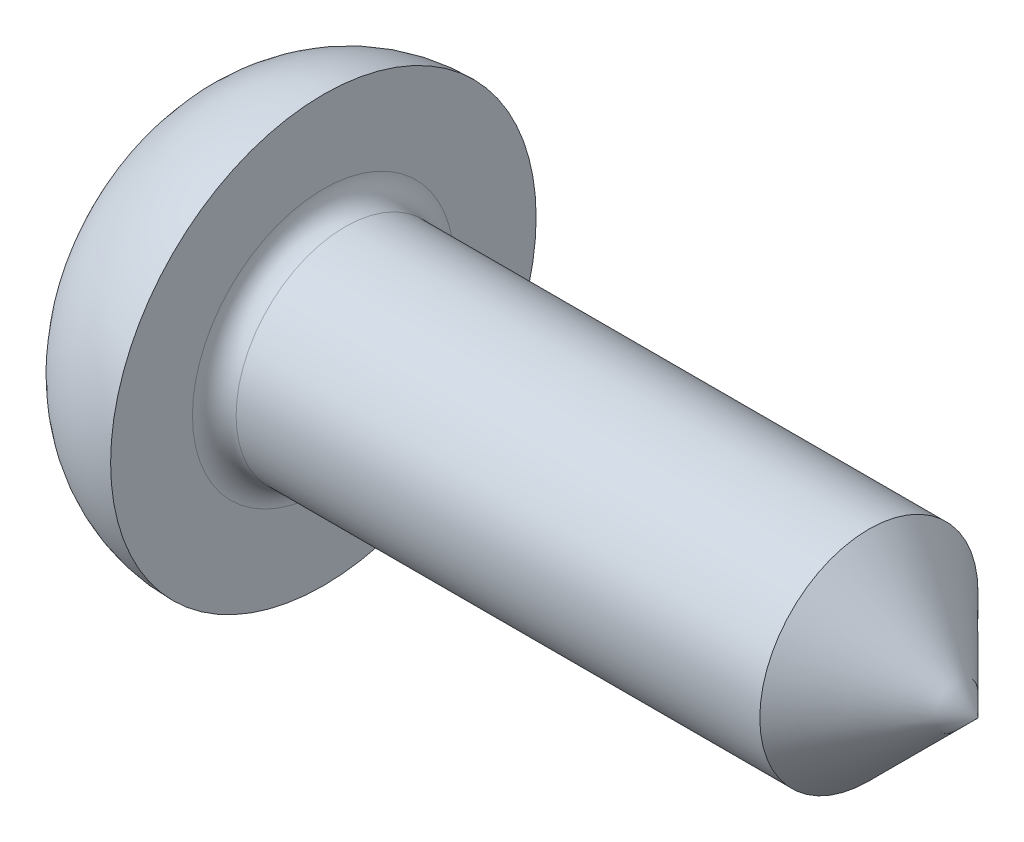
SolidWorks part; units mm, degrees
ref_plane "Front" through (0, 0, 0) normal (0, 0, 1) x (1, 0, 0)
ref_plane "Top" through (0, 0, 0) normal (0, 1, 0) x (1, 0, 0)
ref_plane "Right" through (0, 0, 0) normal (1, 0, 0) x (0, 0, -1)
sketch "Sketch1" plane through (0, 0, 0) normal (0, 1, 0) x (1, 0, 0)
  line L0 (-13.6293, 0) -> (11.3577, 0) construction
  line L1 (1.6, 1) -> (7.6, 1)
  line L2 (7.6, 1) -> (7.6, 0)
  line L3 (1.6, 1) -> (1.6, 1.95)
  line L4 (7.6, 0) -> (0, 0)
  arc A0 (1.6, 1.95) -> (0.4796, 1.4057) centre (1.5877, 0.5501) ccw
  arc A1 (0, 0) -> (0.4796, 1.4057) centre (2.3, 0) cw
  dimension "k" = 1.6
revolve "Revolve1" add sketch "Sketch1" angle 360 about L0
cosmetic thread "ThreadCosmetic1" [suppressed] parameters "l0"=3, "dm"=1.5
fillet "Fillet2" radius 0.2 1 edges at (1.6, 0, 1)
sketch "Sketch4" plane through (0, 0, 0) normal (0, 1, 0) x (1, 0, 0)
  line L0 (4.7828, 0) -> (7.1391, 0) construction
  line L2 (8.3335, 0) -> (8.3335, 21)
  line L3 (8.3335, 21) -> (-13.4, 21)
  line L4 (-13.4, 21) -> (7.6, 0)
  line L5 (7.6, 0) -> (8.3335, 0)
  line L7 (7.6, -1) -> (7.6, 1) construction
  dimension "D1" = 45
  dimension "D2" = 0.7335
  dimension "D3" = 21
revolve "Cut-Revolve1" cut sketch "Sketch4" angle 360 about L0
sketch "Sketch2" plane through (0, 0, 0) normal (1, 0, 0) x (0, 0, -1)
  line L0 (-2.278, 0) -> (2.6944, 0) construction
  line L1 (0, -2.1234) -> (0, 2.1948) construction
  line L2 (-0.3125, 0.3125) -> (-1.25, 0.3125)
  line L3 (0.3125, -1.25) -> (-0.3125, -1.25)
  line L4 (0.3125, -1.25) -> (0.3125, -0.3125)
  line L5 (0.3125, 1.25) -> (-0.3125, 1.25)
  line L6 (-0.3125, -1.25) -> (-0.3125, -0.3125)
  line L7 (1.25, 0.3125) -> (0.3125, 0.3125)
  line L8 (1.25, 0.3125) -> (1.25, -0.3125)
  line L9 (1.25, -0.3125) -> (0.3125, -0.3125)
  line L10 (-1.25, 0.3125) -> (-1.25, -0.3125)
  line L11 (-0.3125, 0.3125) -> (-0.3125, 1.25)
  line L12 (-0.3125, -0.3125) -> (-1.25, -0.3125)
  line L13 (0.3125, 0.3125) -> (0.3125, 1.25)
  point P19 (-0.3125, 0.3125)
  point P22 (0.3125, 0.3125)
  point P27 (-0.3125, -0.3125)
  dimension "D2" = 2.5
  dimension "D3" = 0.625
  dimension "D4" = 0.625
ref_plane "Plane1" through (1.85, 0, 0) normal (1, 0, 0) x (0, 0, -1)
sketch "Sketch5" plane through (1.85, 0, 0) normal (1, 0, 0) x (0, 0, -1)
  point P0 (0, 0)
loft "Cut-Loft1" cut profiles "Sketch5", "Sketch2"
sketch "Sketch6" plane through (0, 0, 0) normal (0, 0, 1) x (1, 0, 0)
  line L0 (3.6, 1.2) -> (3.85, 1.2)
  line L1 (3.85, 1.2) -> (3.85, 1)
  line L2 (3.85, 1) -> (3.725, 0.7835)
  line L3 (3.6, 1) -> (3.725, 0.7835)
  line L4 (3.6, 1.2) -> (3.6, 1)
  line L5 (10.7743, 0) -> (0, 0) construction
  line L6 (3.6, 1) -> (3.85, 1) construction
  line L7 (3.725, 1) -> (3.725, 0.7835) construction
  line L8 (6.6, 1) -> (1.8, 1) construction
  point P5 (3.725, 1.2)
  dimension "D1" = 0.2
  dimension "D3" = 4
revolve "Cut-Revolve10" [suppressed] cut sketch "Sketch6" angle 360 about L5
pattern_linear "LPattern10" [suppressed] count 8 spacing 0.5 along (1, 0, 0) of bodies 105
equation "\"D4@Sketch2\" = \"D3@Sketch2\""
equation "\"D2@Sketch2\" = \"m@Sketch2\""
equation "\"D3@Sketch2\" = \"m@Sketch2\" / 4"
equation "\"D2@Sketch6\" = (  \"d@Sketch1\" - \"dm@ThreadCosmetic1\" )  / 2"
equation "\"D3@Sketch6\" = \"l0@ThreadCosmetic1\" + \"d@Sketch1\" / 2"
equation "\"D3@LPattern10\" = \"D2@Sketch6\" *2"
equation "\"D1@LPattern10\" = \"D3@Sketch6\" / \"D3@LPattern10\""
